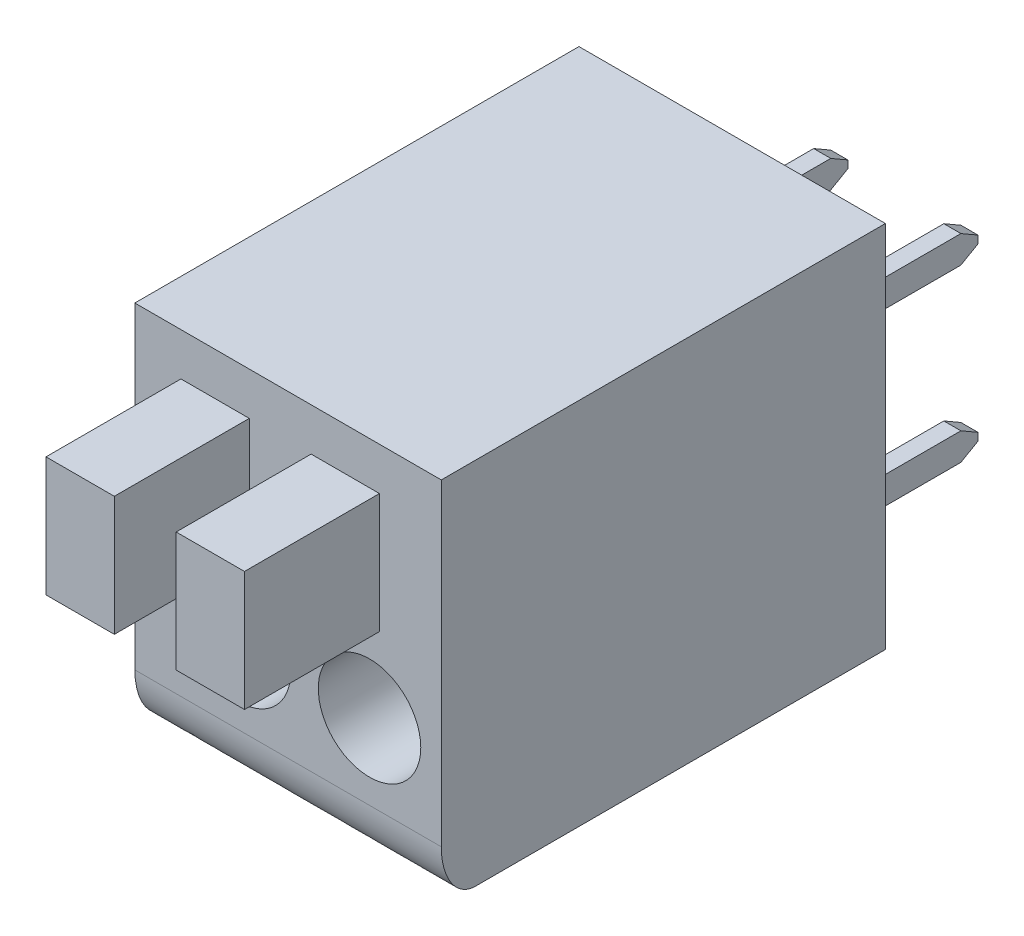
SolidWorks part; units mm, degrees
ref_plane "Спереди" through (0, 0, 0) normal (0, 0, 1) x (1, 0, 0)
ref_plane "Сверху" through (0, 0, 0) normal (0, 1, 0) x (1, 0, 0)
ref_plane "Справа" through (0, 0, 0) normal (1, 0, 0) x (0, 0, -1)
sketch "Эскиз1" plane through (0, 0, 0) normal (0, 0, 1) x (1, 0, 0)
  line L1 (-4.485, -5.4) -> (4.485, -5.4)
  line L2 (-4.485, -5.4) -> (-4.485, 5.4)
  line L3 (-4.485, 5.4) -> (4.485, 5.4)
  line L4 (4.485, -5.4) -> (4.485, 5.4)
  line L5 (-4.485, -5.4) -> (4.485, 5.4) construction
  line L6 (-4.485, 5.4) -> (4.485, -5.4) construction
  point P0 (0, 0)
  dimension "D1" = 8.97
  dimension "D2" = 10.8
extrude "Бобышка-Вытянуть1" add sketch "Эскиз1" along normal blind 13
fillet "Скругление1" radius 1 1 edges at (0, -5.4, 13) second distance 1.5 first distance on face at (0, -5.4, 6.5)
sketch "Эскиз2" plane through (0, 0, 13) normal (0, 0, 1) x (1, 0, 0)
  line L0 (4.485, -3.9) -> (4.485, 5.4) construction
  line L1 (0.675, 0.65) -> (2.675, 0.65)
  line L2 (0.675, 0.65) -> (0.675, 4.15)
  line L3 (0.675, 4.15) -> (2.675, 4.15)
  line L4 (2.675, 0.65) -> (2.675, 4.15)
  line L5 (0.675, 0.65) -> (2.675, 4.15) construction
  line L6 (0.675, 4.15) -> (2.675, 0.65) construction
  line L7 (4.485, 5.4) -> (-4.485, 5.4) construction
  point P0 (1.675, 2.4)
  dimension "D1" = 3.5
  dimension "D2" = 2
  dimension "D3" = 3.81
  dimension "D4" = 4.75
extrude "Бобышка-Вытянуть2" add sketch "Эскиз2" along normal blind 3.95
sketch "Эскиз3" plane through (0, 0, 13) normal (0, 0, 1) x (1, 0, 0)
  line L0 (4.485, -3.9) -> (4.485, 5.4) construction
  circle A0 centre (2.385, -1.686) radius 1.5
  dimension "D1" = 3
  dimension "D2" = 2.1
extrude "Вырез-Вытянуть1" cut sketch "Эскиз3" against normal blind 3.95
sketch "Эскиз4" plane through (0, 0, 0) normal (0, 0, -1) x (-1, 0, 0)
  line L0 (-4.485, 5.4) -> (4.485, 5.4) construction
  line L1 (-3.695, 2.45) -> (-3.195, 2.45)
  line L2 (-3.695, 2.45) -> (-3.695, 3.25)
  line L3 (-3.695, 3.25) -> (-3.195, 3.25)
  line L4 (-3.195, 2.45) -> (-3.195, 3.25)
  line L5 (-3.695, 2.45) -> (-3.195, 3.25) construction
  line L6 (-3.695, 3.25) -> (-3.195, 2.45) construction
  line L7 (-3.195, -1.75) -> (-3.695, -1.75)
  line L8 (-3.195, -1.75) -> (-3.195, -2.55)
  line L9 (-3.195, -2.55) -> (-3.695, -2.55)
  line L10 (-3.695, -1.75) -> (-3.695, -2.55)
  line L11 (-3.195, -1.75) -> (-3.695, -2.55) construction
  line L12 (-3.195, -2.55) -> (-3.695, -1.75) construction
  line L14 (-4.485, -5.4) -> (-4.485, 5.4) construction
  point P0 (-3.445, 2.85)
  point P5 (-3.445, -2.15)
  dimension "D1" = 0.5
  dimension "D2" = 0.8
  dimension "D3" = 5
  dimension "D4" = 2.55
  dimension "D5" = 1.04
extrude "Бобышка-Вытянуть3" add sketch "Эскиз4" along normal blind 3.5
chamfer "Фаска1" distance 0.5 angle 30 4 edges at (3.445, -2.55, -3.5) (3.445, -1.75, -3.5) (3.445, 2.45, -3.5) (3.445, 3.25, -3.5) first distance on face at (3.445, -2.55, -1.75) first distance on face at (3.445, -1.75, -1.75) first distance on face at (3.445, 2.45, -1.75) first distance on face at (3.445, 3.25, -1.75)
pattern_linear "Линейный массив2" count 2 spacing 3.81 along (-1, 0, 0) of "Бобышка-Вытянуть2", "Вырез-Вытянуть1", "Бобышка-Вытянуть3", "Фаска1"
